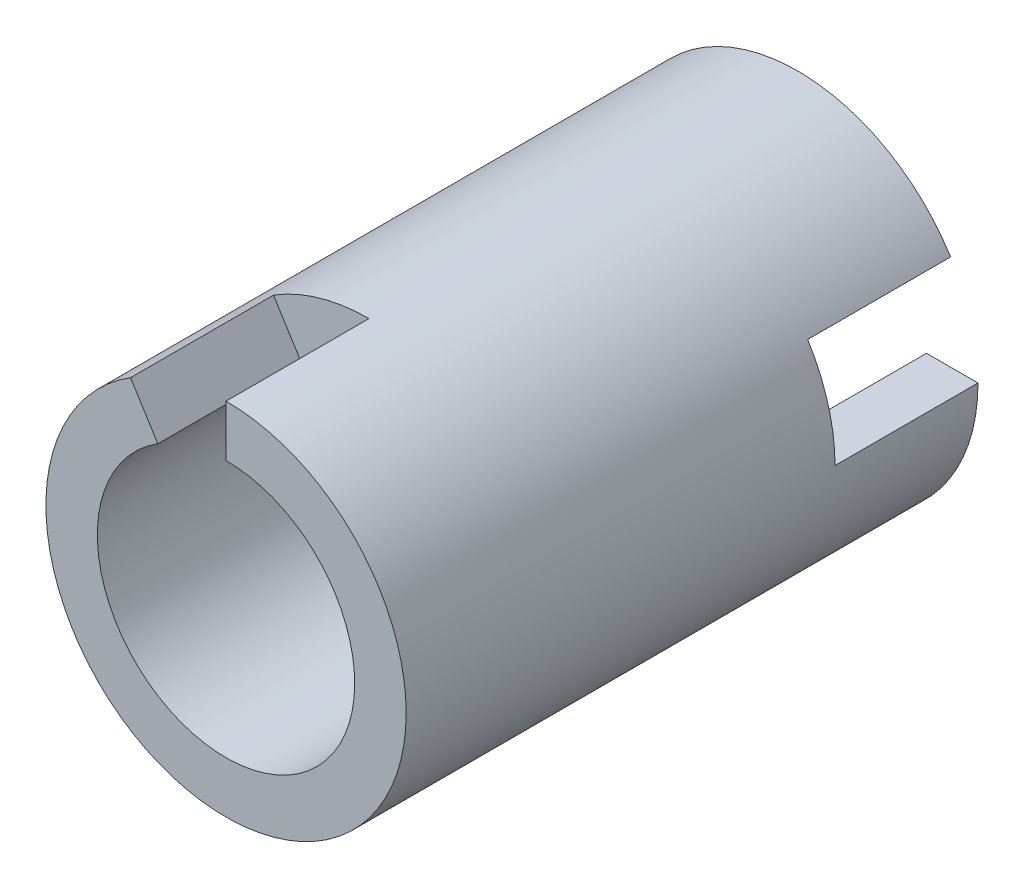
SolidWorks part; units mm, degrees
ref_plane "Front" through (0, 0, 0) normal (0, 0, 1) x (1, 0, 0)
ref_plane "Top" through (0, 0, 0) normal (0, 1, 0) x (1, 0, 0)
ref_plane "Right" through (0, 0, 0) normal (1, 0, 0) x (0, 0, -1)
sketch "Sketch1" plane through (0, 0, 0) normal (0, 0, 1) x (1, 0, 0)
  circle A0 centre (0, 0) radius 6.5
  circle A1 centre (0, 0) radius 4.5
  dimension "D1" = 2
  dimension "D2" = 9
extrude "Boss-Extrude1" add sketch "Sketch1" along normal blind 10 and the other way blind 10
ref_point "Point1"
ref_point "Point2"
ref_axis "Axis1" through (0, 0, 10) along (0, 1, 0)
ref_axis "Axis2" through (0, 0, -10) along (0, 1, 0)
sketch "Sketch2" plane through (0, 0, 10) normal (0, 0, 1) x (1, 0, 0)
  line L0 (-6.23, 9.9701) -> (0, 0)
  line L1 (0, 0) -> (0, 7.5386) construction
  line L3 (0, 0) -> (0, 11.7566)
  arc A0 (0, 11.7566) -> (-6.23, 9.9701) centre (0, 0) ccw
  dimension "D1" = 32
  dimension "D3" = 11.7566
extrude "Cut-Extrude2" cut sketch "Sketch2" against normal blind 5 contours L0 L3 A0
sketch "Sketch4" plane through (0, 0, 10) normal (0, 0, 1) x (1, 0, 0)
  circle A0 centre (0, 0) radius 6.5
  circle A1 centre (0, 0) radius 6.3
  dimension "D2" = 12.6
  dimension "D1" = 0.2
extrude "Cut-Extrude4" cut sketch "Sketch4" against normal through all
sketch "Sketch3" plane through (0, 0, -10) normal (0, 0, 1) x (1, 0, 0)
  line L0 (9.9701, 6.23) -> (0, 0)
  line L3 (0, 0) -> (11.7566, 0)
  arc A0 (11.7566, 0) -> (9.9701, 6.23) centre (0, 0) ccw
  circle A1 centre (0, 0) radius 4.5 construction
  dimension "D1" = 11.7566
  dimension "D2" = 32
extrude "Cut-Extrude3" cut sketch "Sketch3" along normal blind 5 contours L3 A0 L0
